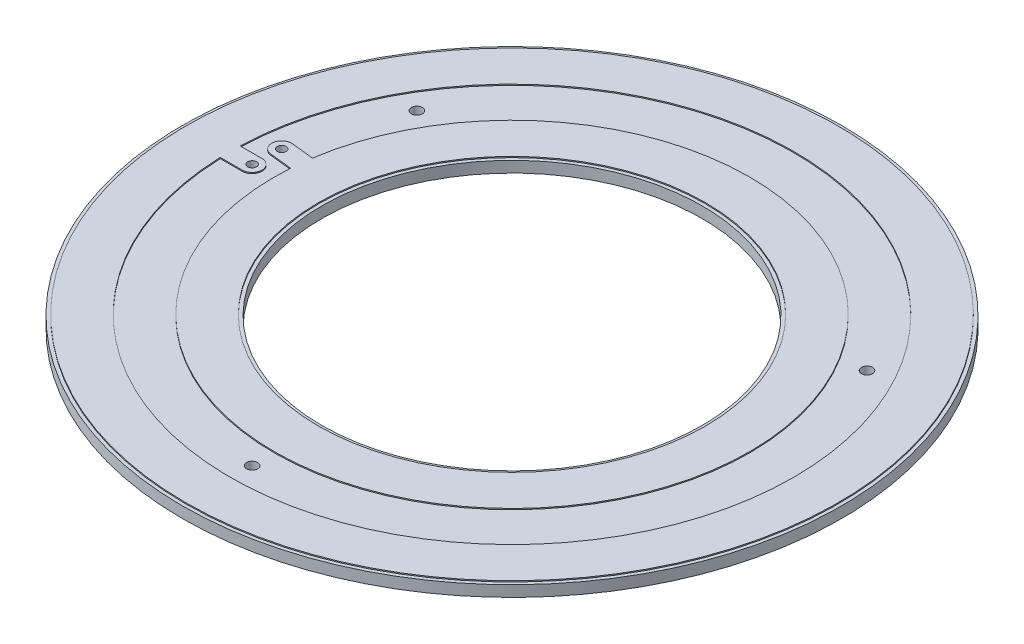
SolidWorks part; units mm, degrees
ref_plane "Спереди" through (0, 0, 0) normal (0, 0, 1) x (1, 0, 0)
ref_plane "Сверху" through (0, 0, 0) normal (0, 1, 0) x (1, 0, 0)
ref_plane "Справа" through (0, 0, 0) normal (1, 0, 0) x (0, 0, -1)
sketch "Эскиз1" plane through (0, 0, 0) normal (0, 1, 0) x (1, 0, 0)
  circle A0 centre (0, 0) radius 17.2
  circle A1 centre (0, 0) radius 29.8
  dimension "D1" = 34.4
  dimension "D2" = 59.6
extrude "Бобышка-Вытянуть1" add sketch "Эскиз1" along normal blind 1
sketch "Эскиз2" plane through (0, 1, 0) normal (0, 1, 0) x (1, 0, 0)
  circle A0 centre (0, 0) radius 29.5
  circle A1 centre (0, 0) radius 25.5
  circle A2 centre (0, 0) radius 21.5
  circle A3 centre (0, 0) radius 17.5
  circle A5 centre (0, 0) radius 17.2 construction
  dimension "D1" = 4
  dimension "D2" = 4
  dimension "D3" = 4
  dimension "D4" = 0.3
extrude "Бобышка-Вытянуть2" add sketch "Эскиз2" along normal blind 0.1 contours A2 A3 | A0 A1 region at (-28.6656, 1, 0) region at (-20.8919, 1, 0)
sketch "Эскиз4" plane through (0, 1, 0) normal (0, 1, 0) x (1, 0, 0)
  line L0 (0, 0) -> (-33.7363, 0) construction
  circle A0 centre (-23.5, 0) radius 0.4
  circle A1 centre (-23.3623, 2.54) radius 0.4
  circle A3 centre (0, 0) radius 23.5 construction
  circle A4 centre (0, 0) radius 21.5 construction
  dimension "D1" = 2
  dimension "D2" = 0.8
  dimension "D3" = 0.8
  dimension "D5" = 47
  dimension "D4" = 2.54
extrude "Вырез-Вытянуть1" cut sketch "Эскиз4" against normal through all
sketch "Эскиз5" plane through (0, 1, 0) normal (0, 1, 0) x (1, 0, 0)
  circle A0 centre (-23.3623, 2.54) radius 0.9
  circle A1 centre (-23.5, 0) radius 0.4 construction
  circle A3 centre (-23.5, 0) radius 0.9
  circle A4 centre (-23.5, 0) radius 0.4
  circle A5 centre (-23.3623, 2.54) radius 0.4 construction
  circle A6 centre (-23.3623, 2.54) radius 0.4
  dimension "D2" = 1.8
  dimension "D1" = 1.8
extrude "Бобышка-Вытянуть3" add sketch "Эскиз5" along normal blind 0.1
ref_axis "Ось1" through (0, 1, 0) along (0, -1, 0)
sketch "Эскиз6" plane through (0, 1, 0) normal (0, 1, 0) x (1, 0, 0)
  line L2 (-23.3623, 2.54) -> (0, 0) construction
  line L5 (-23.5, -0.9) -> (-27.4565, -0.9)
  line L6 (-23.5, 0.9) -> (-27.4565, 0.9)
  line L7 (-27.4565, 0.9) -> (-27.4565, -0.9)
  line L8 (-23.5, -0.9) -> (-24.1108, 0)
  line L9 (-24.1108, 0) -> (-23.5, 0.9)
  line L10 (-23.3623, 1.64) -> (-20.0181, 1.2764)
  line L11 (-20.0181, 1.2764) -> (-19.8247, 3.0554)
  line L12 (-23.1689, 3.419) -> (-19.8247, 3.0554)
  line L13 (-23.3623, 1.64) -> (-22.768, 2.4754)
  line L14 (-22.768, 2.4754) -> (-23.1689, 3.419)
  circle A0 centre (-23.3623, 2.54) radius 0.9 construction
  circle A19 centre (-23.5, 0) radius 0.9 construction
  circle A20 centre (-23.5, 0) radius 0.9 construction
  point P16 (-19.9214, 2.1659)
extrude "Бобышка-Вытянуть4" add sketch "Эскиз6" along normal blind 0.1
sketch "Эскиз7" plane through (0, 1, 0) normal (0, 1, 0) x (1, 0, 0)
  line L0 (0, 0) -> (0, -38.8853) construction
  circle A0 centre (0, 0) radius 23.5 construction
  circle A1 centre (0, -23.5) radius 0.5
  point P3 (0, -23.5)
  dimension "D1" = 47
  dimension "D2" = 1
extrude "Вырез-Вытянуть2" cut sketch "Эскиз7" against normal blind 10
pattern_circular "Круговой массив1" count 3 over 360 about axis through (0, 1, 0) along (0, -1, 0) of "Вырез-Вытянуть2"
